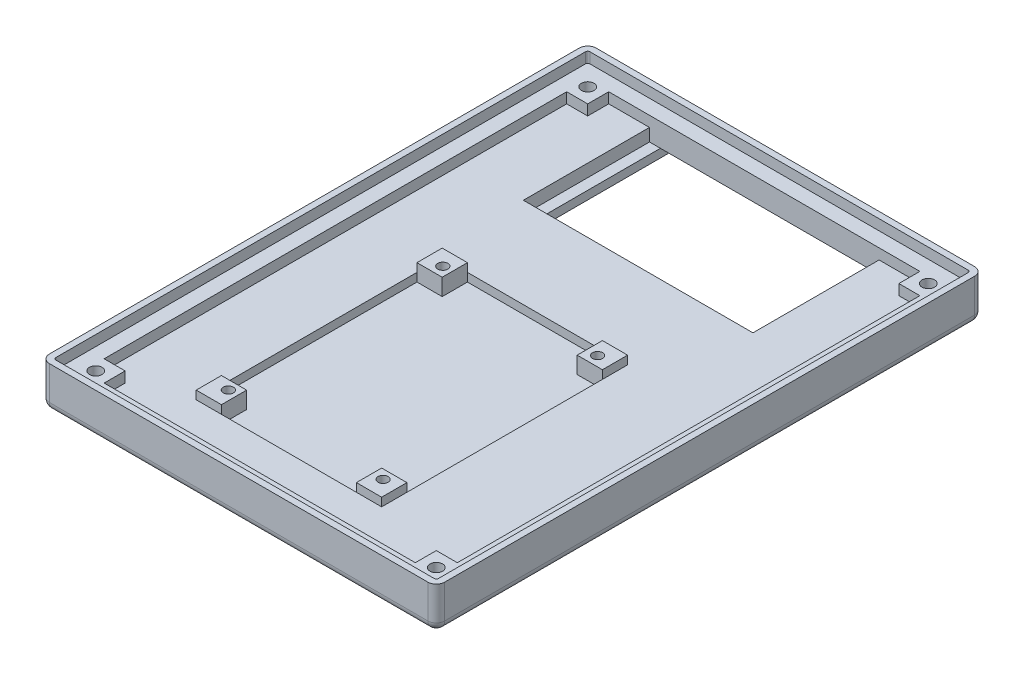
SolidWorks part; units mm, degrees
ref_plane "Front Plane" through (0, 0, 0) normal (0, 0, 1) x (1, 0, 0)
ref_plane "Top Plane" through (0, 0, 0) normal (0, 1, 0) x (1, 0, 0)
ref_plane "Right Plane" through (0, 0, 0) normal (1, 0, 0) x (0, 0, -1)
sketch "Sketch1" plane through (0, 0, 0) normal (0, 1, 0) x (1, 0, 0)
  line L1 (0, 0) -> (94, 0)
  line L2 (0, 0) -> (0, 130)
  line L3 (0, 130) -> (94, 130)
  line L4 (94, 0) -> (94, 130)
  dimension "D1" = 94
  dimension "D2" = 130
extrude "Boss-Extrude1" add sketch "Sketch1" along normal blind 5
sketch "Sketch2" plane through (0, 5, 0) normal (0, 1, 0) x (1, 0, 0)
  line L4 (5, 125) -> (5, 5)
  line L5 (5, 5) -> (89, 5)
  line L6 (89, 5) -> (89, 125)
  line L7 (89, 125) -> (5, 125)
  line L8 (0, 130) -> (0, 0)
  line L9 (0, 0) -> (94, 0)
  line L10 (94, 0) -> (94, 130)
  line L11 (94, 130) -> (0, 130)
  line L12 (0, 130) -> (0, 0)
  line L13 (0, 0) -> (94, 0)
  line L14 (94, 0) -> (94, 130)
  line L15 (94, 130) -> (0, 130)
  dimension "D1" = 0
  dimension "D2" = 5
extrude "Boss-Extrude2" add sketch "Sketch2" along normal blind 5
fillet "Fillet1" radius 2 8 edges at (0, 5, -130) (0, 5, 0) (94, 5, 0) (47, 0, 0) (0, 0, -65) (94, 0, -65) (47, 0, -130) (94, 5, -130)
sketch "Sketch3" plane through (0, 5, 0) normal (0, 1, 0) x (1, 0, 0)
  line L0 (5, 125) -> (5, 5) construction
  line L1 (21.9, 73.5) -> (66, 73.5)
  line L2 (21.9, 73.5) -> (21.9, 15)
  line L3 (21.9, 15) -> (66, 15)
  line L4 (66, 73.5) -> (66, 15)
  line L11 (5, 5) -> (89, 5) construction
  dimension "D1" = 58.5
  dimension "D2" = 44.1
  dimension "D3" = 16.9
  dimension "D4" = 10
extrude "Cut-Extrude1" cut sketch "Sketch3" against normal blind 2
sketch "Sketch5" plane through (0, 3, 0) normal (0, 1, 0) x (1, 0, 0)
  line L0 (66, 73.5) -> (21.9, 73.5) construction
  line L1 (21.9, 73.5) -> (27.9, 73.5)
  line L2 (21.9, 73.5) -> (21.9, 67.5)
  line L3 (21.9, 67.5) -> (27.9, 67.5)
  line L4 (27.9, 73.5) -> (27.9, 67.5)
  line L5 (60, 73.5) -> (66, 73.5)
  line L6 (60, 73.5) -> (60, 67.5)
  line L7 (60, 67.5) -> (66, 67.5)
  line L8 (66, 73.5) -> (66, 67.5)
  line L9 (60, 21) -> (66, 21)
  line L10 (60, 21) -> (60, 15)
  line L11 (60, 15) -> (66, 15)
  line L12 (66, 21) -> (66, 15)
  line L13 (21.9, 21) -> (27.9, 21)
  line L14 (21.9, 21) -> (21.9, 15)
  line L15 (21.9, 15) -> (27.9, 15)
  line L16 (27.9, 21) -> (27.9, 15)
  line L17 (21.9, 73.5) -> (21.9, 15) construction
  line L18 (66, 15) -> (66, 73.5) construction
  line L19 (21.9, 15) -> (66, 15) construction
  dimension "D1" = 6
  dimension "D2" = 6
  dimension "D3" = 6
  dimension "D4" = 6
  dimension "D5" = 6
  dimension "D6" = 6
  dimension "D7" = 6
  dimension "D8" = 6
extrude "Boss-Extrude4" add sketch "Sketch5" along normal blind 4
sketch "Sketch7" plane through (0, 7, 0) normal (0, 1, 0) x (1, 0, 0)
  circle A0 centre (25.71, 69.839) radius 1.2
  circle A1 centre (62.5146, 69.839) radius 1.2
  circle A2 centre (62.5146, 18.8358) radius 1.2
  circle A3 centre (25.71, 18.8358) radius 1.2
extrude "Cut-Extrude2" cut sketch "Sketch7" against normal blind 3
sketch "Sketch8" plane through (0, 5, 0) normal (0, 1, 0) x (1, 0, 0)
  line L1 (19.7, 95) -> (74.3, 95)
  line L2 (19.7, 95) -> (19.7, 125)
  line L3 (19.7, 125) -> (74.3, 125)
  line L4 (74.3, 95) -> (74.3, 125)
  line L5 (89, 125) -> (5, 125) construction
  line L6 (89, 125) -> (5, 125) construction
  point P4 (47, 125)
  point P9 (47, 95)
  dimension "D1" = 30
  dimension "D2" = 54.6
extrude "Cut-Extrude3" cut sketch "Sketch8" against normal blind 3
sketch "Sketch9" plane through (0, 2, 0) normal (0, 1, 0) x (1, 0, 0)
  line L0 (19.7, 95) -> (74.3, 95) construction
  line L1 (22.3, 96.5) -> (71.7, 96.5)
  line L2 (22.3, 96.5) -> (22.3, 123.5)
  line L3 (22.3, 123.5) -> (71.7, 123.5)
  line L4 (71.7, 96.5) -> (71.7, 123.5)
  line L5 (74.3, 125) -> (19.7, 125) construction
  line L6 (19.7, 125) -> (19.7, 95) construction
  line L7 (74.3, 95) -> (74.3, 125) construction
  dimension "D1" = 1.5
  dimension "D2" = 1.5
  dimension "D3" = 2.6
  dimension "D4" = 2.6
extrude "Cut-Extrude4" cut sketch "Sketch9" against normal blind 2
sketch "Sketch10" plane through (0, 0, 0) normal (0, -1, 0) x (1, 0, 0)
  line L1 (71.7, -123.5) -> (22.3, -123.5)
  line L2 (71.7, -123.5) -> (71.7, -130.1195)
  line L3 (71.7, -130.1195) -> (22.3, -130.1195)
  line L4 (22.3, -123.5) -> (22.3, -130.1195)
  line L5 (22.3, -123.5) -> (22.3, -96.5) construction
  line L6 (71.7, -96.5) -> (71.7, -123.5) construction
  line L7 (71.7, -123.5) -> (22.3, -123.5) construction
extrude "Cut-Extrude5" cut sketch "Sketch10" against normal blind 2
sketch "Sketch11" plane through (0, 0, -96.5) normal (0, 0, -1) x (-1, 0, 0)
  line L0 (-22.3, 0) -> (-71.7, 0) construction
  line L1 (-49.5, 1.5) -> (-44.5, 1.5)
  line L2 (-49.5, 1.5) -> (-49.5, 0.5)
  line L3 (-49.5, 0.5) -> (-44.5, 0.5)
  line L4 (-44.5, 1.5) -> (-44.5, 0.5)
  line L5 (-71.7, 0) -> (-71.7, 2) construction
  point P6 (-47, 0)
  point P7 (-47, 0.5)
  point P10 (-71.7, 1)
  point P11 (-49.5, 1)
  dimension "D1" = 5
  dimension "D2" = 1
extrude "Cut-Extrude6" cut sketch "Sketch11" against normal blind 3
sketch "Sketch14" plane through (0, 10, 0) normal (0, 1, 0) x (1, 0, 0)
  line L8 (89, 5) -> (89, 125)
  line L9 (89, 125) -> (5, 125)
  line L10 (5, 125) -> (5, 5)
  line L11 (5, 5) -> (89, 5)
  line L12 (89, 5) -> (89, 125)
  line L13 (89, 125) -> (5, 125)
  line L14 (5, 125) -> (5, 5)
  line L15 (5, 5) -> (89, 5)
  line L20 (92.5, 2) -> (92.5, 128)
  line L21 (92, 128.5) -> (2, 128.5)
  line L22 (1.5, 128) -> (1.5, 2)
  line L23 (2, 1.5) -> (92, 1.5)
  line L24 (92.5, 2) -> (92.5, 128)
  line L25 (92, 128.5) -> (2, 128.5)
  line L26 (1.5, 128) -> (1.5, 2)
  line L27 (2, 1.5) -> (92, 1.5)
  arc A12 (92.5, 128) -> (92, 128.5) centre (92, 128) ccw
  arc A13 (2, 128.5) -> (1.5, 128) centre (2, 128) ccw
  arc A14 (1.5, 2) -> (2, 1.5) centre (2, 2) ccw
  arc A15 (92, 1.5) -> (92.5, 2) centre (92, 2) ccw
  arc A16 (92.5, 128) -> (92, 128.5) centre (92, 128) ccw
  arc A17 (2, 128.5) -> (1.5, 128) centre (2, 128) ccw
  arc A18 (1.5, 2) -> (2, 1.5) centre (2, 2) ccw
  arc A19 (92, 1.5) -> (92.5, 2) centre (92, 2) ccw
  dimension "D1" = 5
  dimension "D2" = 1.5
extrude "Cut-Extrude8" cut sketch "Sketch14" against normal blind 2.5
sketch "Sketch15" plane through (0, 5, 0) normal (0, 1, 0) x (1, 0, 0)
  line L1 (89, 120) -> (84, 120)
  line L2 (89, 120) -> (89, 125)
  line L3 (89, 125) -> (84, 125)
  line L4 (84, 120) -> (84, 125)
  line L5 (10, 120) -> (5, 120)
  line L6 (10, 120) -> (10, 125)
  line L7 (10, 125) -> (5, 125)
  line L8 (5, 120) -> (5, 125)
  line L9 (10, 5) -> (5, 5)
  line L10 (10, 5) -> (10, 10)
  line L11 (10, 10) -> (5, 10)
  line L12 (5, 5) -> (5, 10)
  line L13 (89, 5) -> (84, 5)
  line L14 (89, 5) -> (89, 10)
  line L15 (89, 10) -> (84, 10)
  line L16 (84, 5) -> (84, 10)
  line L17 (89, 125) -> (74.3, 125) construction
  line L18 (89, 5) -> (89, 125) construction
  line L19 (19.7, 125) -> (5, 125) construction
  line L20 (5, 125) -> (5, 5) construction
  line L22 (5, 5) -> (89, 5) construction
  dimension "D1" = 5
  dimension "D2" = 5
  dimension "D3" = 5
  dimension "D4" = 5
  dimension "D5" = 5
  dimension "D6" = 5
  dimension "D7" = 5
  dimension "D8" = 5
extrude "Boss-Extrude5" add sketch "Sketch15" along normal blind 2.5
sketch "Sketch16" plane through (0, 7.5, 0) normal (0, 1, 0) x (1, 0, 0)
  line L0 (10, 120) -> (10, 125) construction
  line L2 (5, 120) -> (10, 120) construction
  line L4 (84, 125) -> (84, 120) construction
  line L5 (89, 10) -> (84, 10) construction
  circle A0 centre (6.5, 123.5) radius 1.5
  circle A1 centre (87.5, 123.5) radius 1.5
  circle A2 centre (87.5, 6.5) radius 1.5
  circle A3 centre (6.5, 6.5) radius 1.5
  point P0 (6.5, 123.5)
  point P1 (87.5, 123.5)
  point P2 (87.5, 6.5)
  point P3 (6.5, 6.5)
  dimension "D5" = 3
  dimension "D6" = 3
  dimension "D7" = 3
  dimension "D8" = 3
  dimension "D1" = 3.5
  dimension "D2" = 3.5
  dimension "D3" = 3.5
  dimension "D4" = 3.5
extrude "Cut-Extrude9" cut sketch "Sketch16" against normal through all
sketch "Sketch17" plane through (0, 0, 0) normal (0, -1, 0) x (1, 0, 0)
  circle A0 centre (6.5, -6.5) radius 2.8
  circle A1 centre (87.5, -6.5) radius 2.8
  circle A2 centre (87.5, -123.5) radius 2.8
  circle A3 centre (6.5, -123.5) radius 2.8
  dimension "D1" = 5.6
  dimension "D2" = 5.6
  dimension "D3" = 5.6
  dimension "D4" = 5.6
extrude "Cut-Extrude10" cut sketch "Sketch17" against normal blind 3
sketch "Sketch18" plane through (0, 0, 0) normal (0, -1, 0) x (1, 0, 0)
  circle A0 centre (6.5, -123.5) radius 4
  circle A1 centre (87.5, -123.5) radius 4
  circle A2 centre (87.5, -6.5) radius 4
  circle A3 centre (6.5, -6.5) radius 4
  circle A4 centre (87.5, -123.5) radius 2.8 construction
  circle A5 centre (6.5, -123.5) radius 2.8 construction
  circle A6 centre (6.5, -6.5) radius 2.8 construction
  circle A7 centre (87.5, -6.5) radius 2.8 construction
  dimension "D1" = 8
  dimension "D2" = 8
  dimension "D3" = 8
  dimension "D4" = 8
extrude "Cut-Extrude11" cut sketch "Sketch18" against normal blind 2
